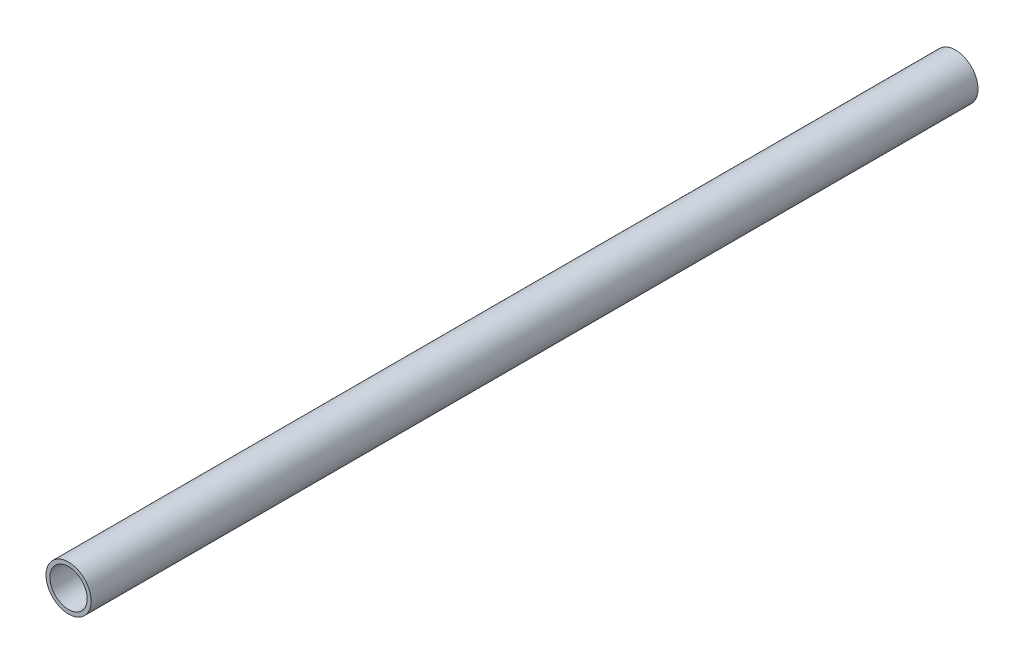
SolidWorks part; units mm, degrees
material "6061-T6 (SS)"
ref_plane "Front Plane" through (0, 0, 0) normal (0, 0, 1) x (1, 0, 0)
ref_plane "Top Plane" through (0, 0, 0) normal (0, 1, 0) x (1, 0, 0)
ref_plane "Right Plane" through (0, 0, 0) normal (1, 0, 0) x (0, 0, -1)
sketch "Sketch1" plane through (0, 0, 0) normal (0, 0, 1) x (1, 0, 0)
  line L0 (-9.525, 0) -> (9.525, 0) construction
  line L1 (0, -9.525) -> (0, 9.525) construction
  circle A0 centre (0, 0) radius 9.525
  circle A1 centre (0, 0) radius 7.874
  point P4 (0, 0)
  point P9 (0, 0)
  point P10 (7.874, 0)
  dimension "D1" = 15.748
  dimension "OD" = 19.05
  dimension "Wall Thickness" = 1.651
sketch "Sketch2" plane through (0, 0, 0) normal (1, 0, 0) x (0, 0, -1)
  line L0 (187.325, 9.525) -> (-187.325, 9.525) construction
  line L1 (0, 9.525) -> (0, -9.525) construction
  point P3 (-165.4175, 9.525)
  point P4 (0, 9.525)
  point P5 (165.4175, 9.525)
  dimension "D1" = 21.9075
  dimension "D2" = 21.9075
  dimension "Length" = 374.65
sketch "Sketch3" plane through (0, 0, 0) normal (0, 0, 1) x (1, 0, 0)
  line L0 (0, -9.525) -> (0, 9.525) construction
  circle A0 centre (0, 0) radius 9.525
  circle A1 centre (0, 0) radius 7.874
  circle A2 centre (0, 0) radius 7.874 construction
extrude "Boss-Extrude1" add sketch "Sketch3" along normal mid plane 374.65
equation "\"D1@Boss-Extrude1\" = \"Length@Sketch2\""
equation "\"D1@Sketch2\"=\"OD@Sketch1\"*1.15"
equation "\"D2@Sketch2\"=\"D1@Sketch2\""
